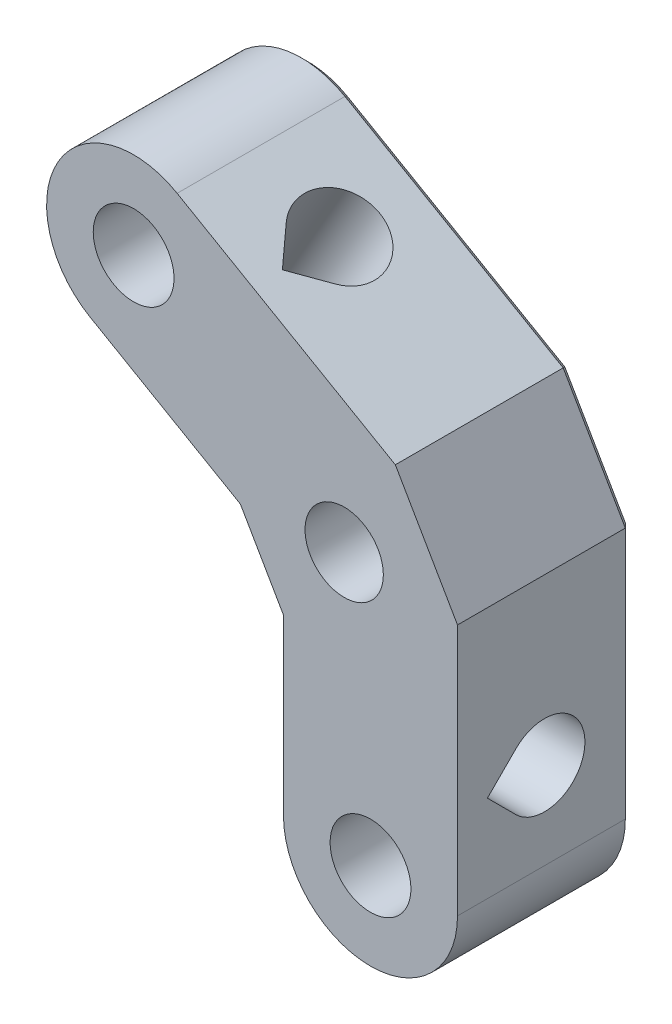
SolidWorks part; units mm, degrees
material "ABS"
ref_plane "Front Plane" through (0, 0, 0) normal (0, 0, 1) x (1, 0, 0)
ref_plane "Top Plane" through (0, 0, 0) normal (0, 1, 0) x (1, 0, 0)
ref_plane "Right Plane" through (0, 0, 0) normal (1, 0, 0) x (0, 0, -1)
ref_plane "Plane4" through (0, 0, 14) normal (0, 0, 1) x (1, 0, 0)
sketch "Sketch1" plane through (0, 0, 14) normal (0, 0, 1) x (1, 0, 0)
  line L0 (7, 0) -> (7, 20.2679)
  line L1 (7, 20.2679) -> (2, 28.9282)
  line L2 (2, 28.9282) -> (-15.5526, 39.0622)
  line L3 (-22.5526, 26.9378) -> (-10.4641, 19.9585)
  line L4 (-10.4641, 19.9585) -> (-7, 13.9585)
  line L5 (-7, 13.9585) -> (-7, 0)
  line L6 (-8.7321, 16.9585) -> (4.5, 24.5981) construction
  arc A0 (-15.5526, 39.0622) -> (-22.5526, 26.9378) centre (-19.0526, 33) ccw
  arc A1 (-7, 0) -> (7, 0) centre (0, 0) ccw
  dimension "D2" = 7
  dimension "D1" = 120
  dimension "D3" = 150
  dimension "D4" = 10
  dimension "D5" = 38.1051
extrude "Boss-Extrude1" add sketch "Sketch1" against normal blind 14
hole_wizard "Hole1" positions "Sketch5" profile "Sketch4" legacy
sketch "Sketch5" plane through (0, 0, 0) normal (0, 0, -1) x (-1, 0, 0)
  point P0 (0, 0)
sketch "Sketch4" plane through (0, 0, 0) normal (1, 0, 0) x (0, 1, 0)
  line L0 (0, 0) -> (0, 14)
  line L1 (0, 14) -> (3.25, 14)
  line L2 (3.25, 14) -> (3.25, 0)
  line L3 (3.25, 0) -> (0, 0)
  line L4 (0, 110) -> (0, -10) construction
  dimension "Diameter" = 6.5
  dimension "Depth" = 14
hole_wizard "Hole2" positions "Sketch7" profile "Sketch6" legacy
sketch "Sketch7" plane through (0, 0, 0) normal (0, 0, -1) x (-1, 0, 0)
  line L0 (0, 0) -> (19.0525, 32.9999) construction
  line L2 (0, 0) -> (22.3725, 0) construction
  point P0 (19.0525, 32.9999)
  dimension "D1" = 38.105
  dimension "D2" = 60
sketch "Sketch6" plane through (-19.0525, 32.9999, 0) normal (1, 0, 0) x (0, 1, 0)
  line L0 (0, 0) -> (0, 14)
  line L1 (0, 14) -> (3.25, 14)
  line L2 (3.25, 14) -> (3.25, 0)
  line L3 (3.25, 0) -> (0, 0)
  line L4 (0, 110) -> (0, -10) construction
  dimension "Diameter" = 6.5
  dimension "Depth" = 14
ref_axis "Axis1" through (-19.0525, 32.9999, 14) along (0, 0, -1)
sketch "Sketch2" plane through (6.0263, 10.4378, 0) normal (-0.5, -0.866, 0) x (0.866, -0.5, 0)
  line L0 (-25.9999, 11.5962) -> (-28.298, 9.2981)
  line L1 (-23.7018, 9.2981) -> (-25.9999, 11.5962)
  line L2 (-32.9999, 14) -> (-32.9999, 0) construction
  line L3 (-19.0415, 7) -> (-31.5924, 7) construction
  line L4 (-19.0415, 0) -> (-19.0415, 14) construction
  arc A0 (-28.298, 9.2981) -> (-23.7018, 9.2981) centre (-25.9999, 7) ccw
  dimension "D1" = 7
  dimension "D2" = 3.25
  dimension "D3" = 45
extrude "Cut-Extrude1" cut sketch "Sketch2" against normal through all
sketch "Sketch3" plane through (-7, 0, 0) normal (-1, 0, 0) x (0, 0, 1)
  line L0 (9.2981, 4.7019) -> (11.5962, 7)
  line L1 (11.5962, 7) -> (9.2981, 9.2981)
  line L2 (7, 0) -> (7, 13.9585) construction
  line L3 (0, 0) -> (14, 0) construction
  line L4 (0, 13.9585) -> (14, 13.9585) construction
  arc A0 (9.2981, 9.2981) -> (9.2981, 4.7019) centre (7, 7) ccw
  dimension "D2" = 3.25
  dimension "D1" = 7
  dimension "D3" = 45
extrude "Cut-Extrude2" cut sketch "Sketch3" against normal through all
sketch "Sketch8" plane through (0, 0, 14) normal (0, 0, 1) x (1, 0, 0)
  line L0 (-8.7321, 16.9585) -> (4.5, 24.5981) construction
  line L1 (-10.4641, 19.9585) -> (-7, 13.9585) construction
  line L2 (7, 20.2679) -> (2, 28.9282) construction
  circle A0 centre (-2.116, 20.7783) radius 3.15
  dimension "D1" = 6.3
extrude "Cut-Extrude3" cut sketch "Sketch8" against normal through all
chamfer "Chamfer1" distance 0.5 angle 45 11 edges at (-3.25, 0, 0) (1.034, 20.7783, 0) (-22.3025, 32.9999, 0) (4.5, 24.5981, 0) (7, 10.134, 0) (0, -7, 0) (-7, 6.9793, 0) (-8.7321, 16.9585, 0) (-16.5083, 23.4482, 0) (-25.1147, 36.5, 0) (-6.7763, 33.9952, 0)
